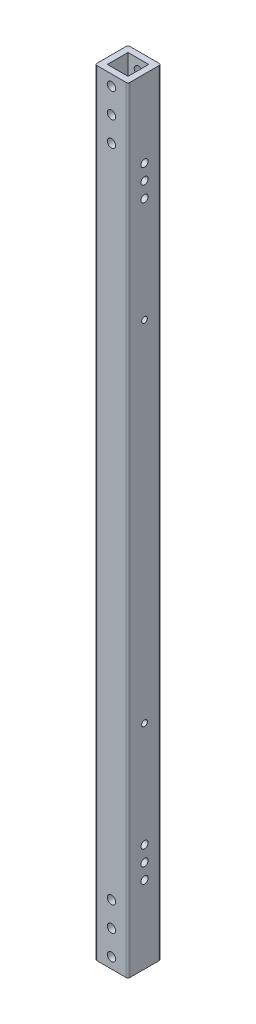
SolidWorks part; units mm, degrees
material "1060 Alloy"
ref_plane "Front Plane" through (0, 0, 0) normal (0, 0, 1) x (1, 0, 0)
ref_plane "Top Plane" through (0, 0, 0) normal (0, 1, 0) x (1, 0, 0)
ref_plane "Right Plane" through (0, 0, 0) normal (1, 0, 0) x (0, 0, -1)
sketch "Sketch1" plane through (0, 0, 0) normal (0, 1, 0) x (1, 0, 0)
  line L0 (-7.9375, 7.9375) -> (7.9375, 7.9375)
  line L1 (-12.7, -12.7) -> (12.7, -12.7)
  line L2 (-12.7, -12.7) -> (-12.7, 12.7)
  line L3 (-12.7, 12.7) -> (12.7, 12.7)
  line L4 (12.7, -12.7) -> (12.7, 12.7)
  line L5 (-12.7, -12.7) -> (12.7, 12.7) construction
  line L6 (-12.7, 12.7) -> (12.7, -12.7) construction
  line L7 (7.9375, -7.9375) -> (7.9375, 7.9375)
  line L8 (-7.9375, -7.9375) -> (7.9375, -7.9375)
  line L9 (-7.9375, -7.9375) -> (-7.9375, 7.9375)
  point P0 (0, 0)
  dimension "D1" = 25.4
  dimension "D2" = 4.7625
extrude "Boss-Extrude1" add sketch "Sketch1" along normal mid plane 596
fillet "Fillet1" radius 1.5 4 edges at (-12.7, 0, -12.7) (12.7, 0, -12.7) (-12.7, 0, 12.7) (12.7, 0, 12.7)
hole_wizard "1/4 (0.25) Diameter Hole1" positions "3DSketch3" profile "Sketch3" hole size "1/4" standard "ANSI Inch" end condition through all
sketch3d "3DSketch3"
  line L0 (0.0118, 289.825, -12.7) -> (0.0118, 251.825, -12.7) construction
  line L2 (11.2, 298, -12.7) -> (-11.2, 298, -12.7) construction
  line L3 (-12.7, 298, -11.2) -> (-12.7, -298, -11.2) construction
  point P0 (0.0118, 289.825, -12.7)
  point P2 (0.0118, 270.825, -12.7)
  point P4 (0.0118, 251.825, -12.7)
  point P16 (0.0118, 270.825, -12.7)
  dimension "D1" = 38
  dimension "D2" = 8.175
  dimension "D3" = 12.8
sketch "Sketch3" plane through (0.0118, 289.825, -12.7) normal (1, 0, 0) x (0, 1, 0)
  line L0 (0, 0) -> (0, 25.4)
  line L1 (0, 25.4) -> (3.175, 25.4)
  line L2 (3.175, 25.4) -> (3.175, 0)
  line L5 (3.175, 0) -> (0, 0)
  line L11 (0, -6.35) -> (0, 107.95) construction
  dimension "Thru Hole Dia." = 6.35
  dimension "Thru Hole Depth" = 25.4
mirror "Mirror1" about plane through (0, 0, 0) normal (0, 1, 0) of "1/4 (0.25) Diameter Hole1"
sketch "Sketch4" plane through (-12.7, 0, 0) normal (-1, 0, 0) x (0, 0, 1)
  line L0 (-11.2, 298) -> (11.2, 298) construction
  line L1 (-1000, 0) -> (49000, 0) construction
  line L3 (-22.8667, 248.65) -> (51.7546, 248.65) construction
  circle A1 centre (0, 134.3) radius 2.2
  circle A2 centre (0, -134.3) radius 2.2
  circle A3 centre (0, 238.65) radius 2.75
  circle A4 centre (0, 226.9) radius 2.75
  circle A5 centre (0, 215.15) radius 2.75
  circle A6 centre (0, -215.15) radius 2.75
  circle A7 centre (0, -226.9) radius 2.75
  circle A8 centre (0, -238.65) radius 2.75
  point P0 (0, 134.3)
  point P6 (0, 298)
  point P23 (1.0783, 238.65)
  point P25 (0, 0)
  dimension "D2" = 4.4
  dimension "D3" = 5.5
  dimension "D4" = 11.75
  dimension "D5" = 11.75
  dimension "D6" = 10
  dimension "D1" = 163.7
extrude "Cut-Extrude1" cut sketch "Sketch4" against normal through all
